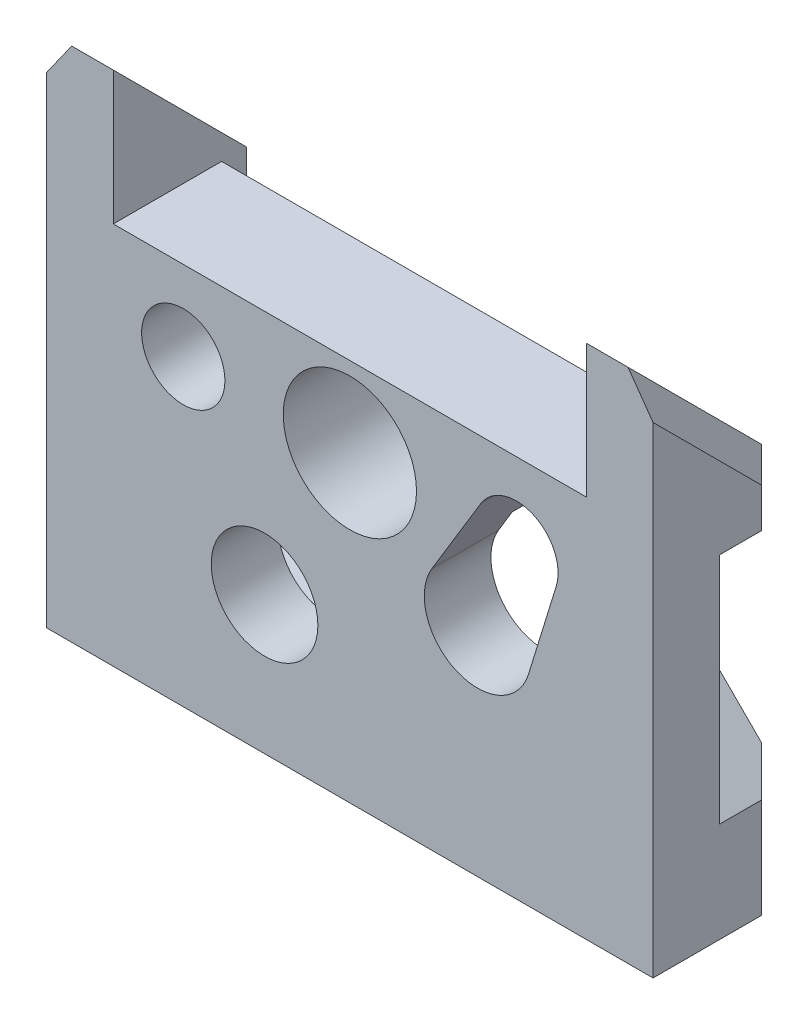
SolidWorks part; units mm, degrees
ref_plane "Front Plane" through (0, 0, 0) normal (0, 0, 1) x (1, 0, 0)
ref_plane "Top Plane" through (0, 0, 0) normal (0, 1, 0) x (1, 0, 0)
ref_plane "Right Plane" through (0, 0, 0) normal (1, 0, 0) x (0, 0, -1)
ref_plane "Switch Base" through (0, 0, -4) normal (0, 0, 1) x (1, 0, 0)
ref_plane "Plane2" through (0, 0, -6) normal (0, 0, 1) x (1, 0, 0)
sketch "Outside Frame" plane through (0, 0, -4) normal (0, 0, 1) x (1, 0, 0)
  line L1 (9.1, -9.1) -> (-9.1, -9.1)
  line L2 (9.1, -9.1) -> (9.1, 9.1)
  line L3 (9.1, 9.1) -> (-9.1, 9.1)
  line L4 (-9.1, -9.1) -> (-9.1, 9.1)
  line L5 (9.1, -9.1) -> (-9.1, 9.1) construction
  line L6 (9.1, 9.1) -> (-9.1, -9.1) construction
  line L7 (7.1, -7.1) -> (-7.1, -7.1)
  line L8 (7.1, -7.1) -> (7.1, 7.1)
  line L9 (7.1, 7.1) -> (-7.1, 7.1)
  line L10 (-7.1, -7.1) -> (-7.1, 7.1)
  line L11 (7.1, -7.1) -> (-7.1, 7.1) construction
  line L12 (7.1, 7.1) -> (-7.1, -7.1) construction
  point P0 (0, 0)
  point P5 (0, 0)
  dimension "D1" = 14.2
  dimension "D2" = 2
extrude "Outer Frame Extrude" add sketch "Outside Frame" along normal blind 4 and the other way blind 2 separate body
sketch "Switch Pin Holes" plane through (0, 0, -4) normal (0, 0, 1) x (1, 0, 0)
  line L0 (5, 0) -> (-5, 0) construction
  circle A0 centre (0, 0) radius 2
  circle A1 centre (-5, 0) radius 1.25
  circle A2 centre (5, 0) radius 1.25
  point P12 (0, 0)
  dimension "D1" = 4
  dimension "D3" = 2.5
  dimension "D2" = 10
sketch "Hotswap Well" plane through (0, 0, -6) normal (0, 0, -1) x (-1, 0, 0)
  line L0 (-10, -1.1) -> (-2.3558, -1.1)
  line L2 (0, -2.6) -> (5, -2.6)
  line L3 (5, -2.6) -> (5, -3.35)
  line L4 (5, -3.35) -> (10, -3.35)
  line L5 (10, -3.35) -> (10, -6.9)
  line L6 (10, -6.9) -> (-6, -6.9)
  line L7 (-6, -6.9) -> (-6, -4.1)
  line L8 (-6, -4.1) -> (-10, -4.1)
  line L9 (-10, -4.1) -> (-10, -1.1)
  line L10 (0, 0) -> (0, -9.97) construction
  line L11 (-10, -2.6) -> (0, -2.6) construction
  line L12 (0, -2.6) -> (10, -2.6) construction
  line L13 (10, -2.6) -> (10, -3.35) construction
  arc A0 (-2.3558, -1.1) -> (0, -2.6) centre (0, 0) ccw
  circle A1 centre (0, 0) radius 2 construction
  dimension "D5" = 4.3
  dimension "D1" = 3
  dimension "D2" = 20
  dimension "D3" = 6
  dimension "D4" = 2.6
  dimension "D6" = 5
  dimension "D7" = 0.75
sketch "Hotswap Holes" plane through (0, 0, 0) normal (0, 0, 1) x (1, 0, 0)
  line L0 (10, -2.6) -> (0, -2.6) construction
  line L1 (3.9309, 0.6477) -> (2.4655, -1.7709)
  line L2 (5.3632, -3.0705) -> (6.1947, -0.3676)
  circle A0 centre (-2.5601, -4.9653) radius 1.6
  arc A1 (4.5122, -1.1509) -> (4.4649, -1.1297) centre (3.8339, -2.6) ccw
  circle A2 centre (5, 0) radius 1.25 construction
  arc A3 (6.1947, -0.3676) -> (3.9309, 0.6477) centre (5, 0) ccw
  arc A4 (4.4649, -1.1297) -> (4.5122, -1.1509) centre (5, 0) ccw
  arc A5 (2.4655, -1.7709) -> (5.3632, -3.0705) centre (3.8339, -2.6) ccw
  dimension "D1" = 3.2
sketch "Hotswap Base" plane through (0, 0, -4) normal (0, 0, 1) x (1, 0, 0)
  line L0 (-9.1, 9.1) -> (-9.1, -9.1) construction
  line L1 (-9.1, 2.4) -> (9.1, 2.4)
  line L2 (-9.1, 2.4) -> (-9.1, -9.1)
  line L3 (-9.1, -9.1) -> (9.1, -9.1)
  line L4 (9.1, 2.4) -> (9.1, -9.1)
  dimension "D1" = 11.5
extrude "Hotswap Base Block" add sketch "Hotswap Base" against normal blind 4
sketch "Sketch1" plane through (0, 0, 0) normal (1, 0, 0) x (0, 0, -1)
  line L0 (4, 55) -> (4, -55) construction
  line L1 (4, 9.1) -> (6, 9.1)
  line L2 (4, 9.1) -> (4, 2.4)
  line L3 (4, 2.4) -> (6, 2.4)
  line L4 (6, 9.1) -> (6, 2.4)
  line L5 (6, 9.1) -> (0, 9.1) construction
  line L6 (6, 55) -> (6, -55) construction
  line L7 (8, 2.4) -> (6, 2.4) construction
extrude "Cut-Extrude4" cut sketch "Sketch1" against normal through all both and the other way through all
extrude "Cut-Extrude1" cut sketch "Hotswap Well" along normal blind 4
extrude "Switch Holes" cut sketch "Switch Pin Holes" against normal offset from surface (3.6 mm away) 0.4 up to face at (-0.9282, -1.2054, -8)
extrude "Cut-Extrude3" cut sketch "Hotswap Holes" against normal up to surface (7.6 mm away) contours L2 A3 L1 A5 | A0 up to face at (5, 0.075, -7.6)
chamfer "Chamfer1" distance 2 angle 45 4 edges at (9.1, -1.1, -7) (9.1, -4.1, -7) (-9.1, -6.9, -7) (-9.1, -3.35, -7)
chamfer "Chamfer2" distance 4 angle 45 2 edges at (-8.1, 2.4, -4) (8.1, 2.4, -4)
fillet "Fillet1" radius 0.35 5 edges at (2.3558, -1.1, -7) (-5, -3.35, -7) (-5, -2.6, -7) (6, -6.9, -7) (6, -4.1, -7)
chamfer "Chamfer3" distance 0.75 angle 45 8 edges at (9.1, 1.65, -8) (-9.1, 0.525, -8) (-9.1, -9, -8) (9.1, -7.6, -8) (0, -9.1, -8) (0, 2.4, -8) (9.1, 4.4, -6) (-9.1, 4.4, -6)
split "Split1" trim tools "Switch Base" bodies to split 107 resulting bodies 110
